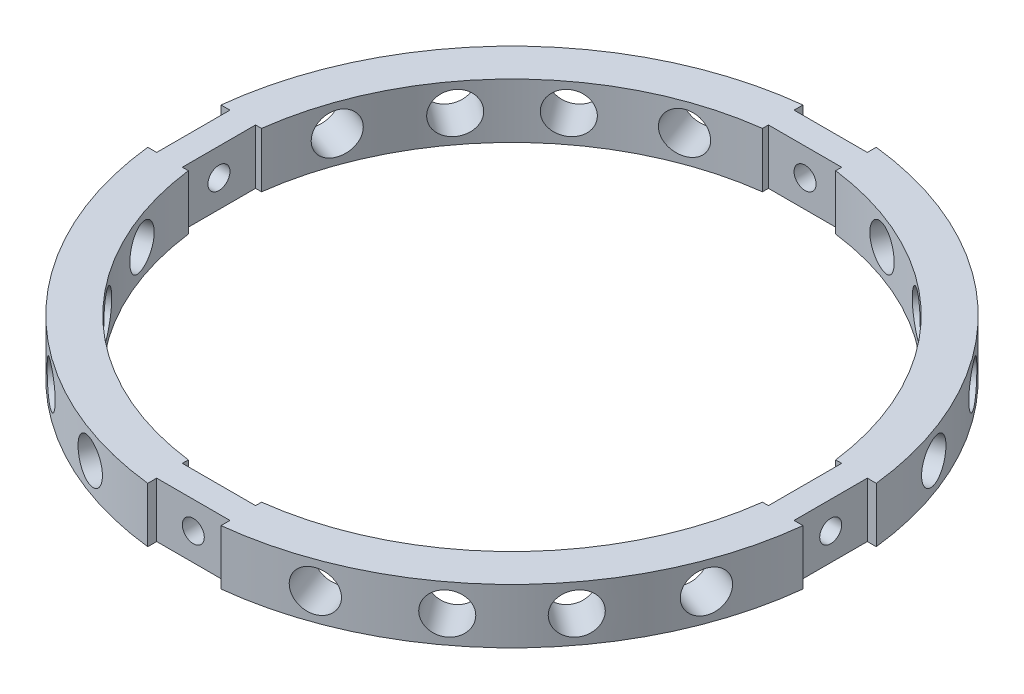
SolidWorks part; units mm, degrees
other "Markup1"
sketch "Sketch19"
material "1060 Alloy"
ref_plane "Front Plane" through (0, 0, 0) normal (0, 0, 1) x (1, 0, 0)
ref_plane "Top Plane" through (0, 0, 0) normal (0, 1, 0) x (1, 0, 0)
ref_plane "Right Plane" through (0, 0, 0) normal (1, 0, 0) x (0, 0, -1)
sketch "Sketch1" plane through (0, 0, 0) normal (0, 1, 0) x (1, 0, 0)
  circle A0 centre (0, 0) radius 90
  circle A1 centre (0, 0) radius 79
  dimension "OuterDiameter" = 180
  dimension "InnerDiameter" = 158
extrude "Boss-Extrude1" add sketch "Sketch1" along normal blind 7.5 and the other way blind 7.5
sketch "Sketch5" plane through (0, 7.5, 0) normal (0, 1, 0) x (1, 0, 0)
  line L0 (0, 0) -> (53.7588, 53.7588) construction
  line L1 (0.2616, 0.2616) -> (60.0121, 60.0121) construction
  line L2 (-121.3123, 0) -> (150.1577, 0) construction
  circle A0 centre (60.0121, 60.0121) radius 3
  circle A1 centre (60.0121, -59.4889) radius 3
  circle A2 centre (-59.4889, -59.4889) radius 3
  circle A3 centre (-59.4889, 60.0121) radius 3
  dimension "MountingBoltDiameter" = 6
  dimension "D2" = 84.5
  dimension "D3" = 45
sketch "Sketch6" plane through (0, 7.5, 0) normal (0, 1, 0) x (1, 0, 0)
  line L0 (0, -83.4209) -> (0, 77.0416) construction
  line L1 (-88.8703, 0) -> (103.6253, 0) construction
  line L2 (-10, -87) -> (10, -87)
  line L3 (-10, 90) -> (10, 90)
  line L4 (-10, 90) -> (-10, 87)
  line L5 (-10, 87) -> (10, 87)
  line L6 (10, 90) -> (10, 87)
  line L7 (-10, 90) -> (10, 87) construction
  line L8 (-10, 87) -> (10, 90) construction
  line L9 (10, -90) -> (10, -87)
  line L10 (-10, -90) -> (10, -90)
  line L11 (-10, -90) -> (-10, -87)
  line L12 (0, 0) -> (60.635, 60.635) construction
  line L13 (87, -10) -> (87, 10)
  line L14 (90, 10) -> (87, 10)
  line L15 (90, -10) -> (90, 10)
  line L16 (90, -10) -> (87, -10)
  line L17 (-90, -10) -> (-87, -10)
  line L18 (-90, -10) -> (-90, 10)
  line L19 (-90, 10) -> (-87, 10)
  line L20 (-87, -10) -> (-87, 10)
  point P5 (0, 88.5)
  point P10 (0, 90)
  dimension "RailWidth" = 20
  dimension "D1" = 90
  dimension "D2" = 3
extrude "Cut-Extrude4" cut sketch "Sketch6" against normal through all
sketch "Sketch7" plane through (-87, 0, 0) normal (-1, 0, 0) x (0, 0, 1)
  line L0 (0, 14.1508) -> (0, -8.7308) construction
  line L1 (-87, 0) -> (87, 0) construction
  line L2 (-87, -7.5) -> (-87, 7.5) construction
  line L3 (87, -7.5) -> (87, 7.5) construction
  circle A1 centre (0, 0) radius 3
  point P9 (0, 0)
  dimension "D1" = 6
extrude "Cut-Extrude5" cut sketch "Sketch7" against normal through all
sketch "Sketch12" plane through (0, 0, 87) normal (0, 0, 1) x (1, 0, 0)
  line L0 (0, 13.7216) -> (0, -16.0459) construction
  line L1 (-75.3828, 0) -> (78.5537, 0) construction
  circle A1 centre (0, 0) radius 3
  point P5 (0, 0)
  dimension "D1" = 6
extrude "Cut-Extrude8" cut sketch "Sketch12" against normal through all
sketch "Sketch13" plane through (0, 7.5, 0) normal (0, 1, 0) x (1, 0, 0)
  line L0 (0, -87.0356) -> (0, 86.4553) construction
  line L1 (-98.9563, 0) -> (122.4152, 0) construction
  line L2 (0, 0) -> (96.5387, 96.5387) construction
  line L3 (-10, -80) -> (10, -80)
  line L4 (-10, -80) -> (-10, -77)
  line L5 (-10, -77) -> (10, -77)
  line L6 (10, -80) -> (10, -77)
  line L7 (-10, -80) -> (10, -77) construction
  line L8 (-10, -77) -> (10, -80) construction
  line L9 (-10, 77) -> (10, 77)
  line L10 (10, 80) -> (10, 77)
  line L11 (-10, 80) -> (10, 80)
  line L12 (-10, 80) -> (-10, 77)
  line L13 (-77, -10) -> (-77, 10)
  line L14 (-80, 10) -> (-77, 10)
  line L15 (-80, -10) -> (-80, 10)
  line L16 (-80, -10) -> (-77, -10)
  line L17 (80, -10) -> (77, -10)
  line L18 (80, -10) -> (80, 10)
  line L19 (80, 10) -> (77, 10)
  line L20 (77, -10) -> (77, 10)
  point P7 (0, -78.5)
  dimension "D1" = 20
  dimension "D3" = 77
  dimension "D2" = 80
  dimension "D4" = 45
extrude "Cut-Extrude9" cut sketch "Sketch13" against normal through all
sketch "Sketch14" plane through (0, 7.5, 0) normal (0, 1, 0) x (1, 0, 0)
  line L0 (0, 98.1591) -> (0, -98.1685) construction
  line L1 (-142.6508, 0) -> (156.3484, 0) construction
  line L2 (0, -0.0047) -> (84.5738, 30.7777) construction
  line L3 (0, -0.0047) -> (30.7833, 84.5718) construction
  line L4 (-0.0047, 0) -> (84.5718, -30.7833) construction
  line L5 (-0.0047, 0) -> (30.7777, -84.5738) construction
  line L6 (0, 0.0047) -> (-30.7833, -84.5718) construction
  line L7 (0, 0.0047) -> (-84.5738, -30.7777) construction
  line L8 (0.0047, 0) -> (-84.5718, 30.7833) construction
  line L9 (0.0047, 0) -> (-30.7777, 84.5738) construction
  line L12 (0, -0.0047) -> (54.1656, 71.8755) construction
  line L13 (0, -0.0047) -> (71.8794, 54.1604) construction
  line L14 (-0.0047, 0) -> (54.1604, -71.8794) construction
  line L15 (-0.0047, 0) -> (71.8755, -54.1656) construction
  line L16 (0, 0.0047) -> (-71.8794, -54.1604) construction
  line L17 (0, 0.0047) -> (-54.1656, -71.8755) construction
  line L18 (0.0047, 0) -> (-54.1604, 71.8794) construction
  line L19 (0.0047, 0) -> (-71.8755, 54.1656) construction
  arc A0 (89.4427, 10) -> (10, 89.4427) centre (0, 0) ccw construction
  point P23 (0, 0)
  point P35 (0, 0)
  dimension "D1" = 20
  dimension "D2" = 20
  dimension "D4" = 17
  dimension "D5" = 17
  dimension "D3" = 4
  dimension "D6" = 4
ref_plane "Plane1" through (0.0041, 0, -0.0015) normal (0.9397, 0, -0.342) x (-0.342, 0, -0.9397)
ref_plane "Plane2" through (0.0005, 0, -0.0015) normal (0.342, 0, -0.9397) x (-0.9397, 0, -0.342)
ref_plane "Plane3" through (-0.0015, 0, -0.0041) normal (-0.342, 0, -0.9397) x (-0.9397, 0, 0.342)
ref_plane "Plane4" through (-0.0015, 0, -0.0005) normal (-0.9397, 0, -0.342) x (-0.342, 0, 0.9397)
sketch "Sketch15" plane through (0.0041, 0, -0.0015) normal (0.9397, 0, -0.342) x (-0.342, 0, -0.9397)
  line L0 (-103.0218, 0) -> (121.7701, 0) construction
  circle A0 centre (0, 0) radius 5.565
  dimension "D1" = 11.13
extrude "Cut-Extrude10" cut sketch "Sketch15" against normal through all and the other way through all
sketch "Sketch16" plane through (0.0005, 0, -0.0015) normal (0.342, 0, -0.9397) x (-0.9397, 0, -0.342)
  line L0 (-116.6479, 0) -> (178.0546, 0) construction
  circle A0 centre (0, 0) radius 5.565
  dimension "D1" = 11.13
extrude "Cut-Extrude11" cut sketch "Sketch16" against normal through all and the other way through all
sketch "Sketch17" plane through (-0.0015, 0, -0.0041) normal (-0.342, 0, -0.9397) x (-0.9397, 0, 0.342)
  line L0 (-115.4594, 0) -> (154.8622, 0) construction
  circle A0 centre (0, 0) radius 5.565
  dimension "D1" = 11.13
extrude "Cut-Extrude12" cut sketch "Sketch17" against normal through all and the other way through all
sketch "Sketch18" plane through (-0.0015, 0, -0.0005) normal (-0.9397, 0, -0.342) x (-0.342, 0, 0.9397)
  line L0 (-110.4319, 0) -> (111.3832, 0) construction
  circle A0 centre (0.4757, 0) radius 5.565
  dimension "D1" = 11.13
extrude "Cut-Extrude13" cut sketch "Sketch18" against normal through all and the other way through all
ref_plane "Plane5" through (0.003, 0, -0.0023) normal (0.7986, 0, -0.6018) x (-0.6018, 0, -0.7986)
sketch "Sketch20" plane through (0.003, 0, -0.0023) normal (0.7986, 0, -0.6018) x (-0.6018, 0, -0.7986)
  line L0 (-125.5135, 0) -> (138.902, 0) construction
  circle A0 centre (0, 0) radius 5.565
  dimension "D1" = 11.13
extrude "Cut-Extrude14" cut sketch "Sketch20" against normal through all and the other way through all
ref_plane "Plane6" through (0.0017, 0, -0.0023) normal (0.6018, 0, -0.7986) x (-0.7986, 0, -0.6018)
sketch "Sketch21" plane through (0.0017, 0, -0.0023) normal (0.6018, 0, -0.7986) x (-0.7986, 0, -0.6018)
  line L0 (-98.8665, 0) -> (107.0384, 0) construction
  circle A0 centre (0, 0) radius 5.565
  dimension "D1" = 11.13
extrude "Cut-Extrude15" cut sketch "Sketch21" against normal through all and the other way through all
ref_plane "Plane7" through (0.0023, 0, 0.0017) normal (0.7986, 0, 0.6018) x (0.6018, 0, -0.7986)
ref_plane "Plane8" through (0.0023, 0, 0.003) normal (0.6018, 0, 0.7986) x (0.7986, 0, -0.6018)
sketch "Sketch22" plane through (0.0023, 0, 0.0017) normal (0.7986, 0, 0.6018) x (0.6018, 0, -0.7986)
  line L0 (-93.4645, 0) -> (99.5843, 0) construction
  circle A0 centre (0, 0) radius 5.565
  dimension "D1" = 11.13
extrude "Cut-Extrude16" cut sketch "Sketch22" against normal through all and the other way through all
sketch "Sketch23" plane through (0.0023, 0, 0.003) normal (0.6018, 0, 0.7986) x (0.7986, 0, -0.6018)
  line L0 (-99.4077, 0) -> (99.855, 0) construction
  circle A0 centre (0, 0) radius 5.565
  dimension "D1" = 11.13
extrude "Cut-Extrude17" cut sketch "Sketch23" against normal through all and the other way through all
equation "\"InternalDiameter\"= 158mm"
equation "\"ExternalDiameter\"= 180mm"
equation "\"InnerDiameter@Sketch1\"= \"InternalDiameter\""
equation "\"OuterDiameter@Sketch1\"= \"ExternalDiameter\""
equation "\"MountingBoltDiameter\"= 6mm"
equation "\"NumberOfMountingBolts\"= 4"
equation "\"MountingBoltDiameter@Sketch5\"= \"MountingBoltDiameter\""
equation "\"D1@Sketch5\"= \"NumberOfMountingBolts\""
equation "\"D2@Sketch5\"= 0.25 * ( \"InternalDiameter\" + \"ExternalDiameter\" )"
equation "\"RailBoltDiameter\"= 6mm"
equation "\"RailBoltSpacing\"= 12mm"
equation "\"RailWidth\"= 10mm"
equation "\"RailWidth@Sketch6\"= \"RailWidth\" * 2"
equation "\"D1@Sketch13\"= \"RailWidth\" * 2"
equation "\"RailDepth\"= 2mm"
equation "\"D3@Sketch13\"= \"InternalDiameter\" / 2 - \"RailDepth\""
equation "\"D2@Sketch13\"= \"InternalDiameter\" / 2 + \"RailDepth\" / 2"
equation "\"D1@Sketch6\"= \"ExternalDiameter\" / 2"
equation "\"D2@Sketch6\"= \"RailDepth\" * 1.5"
equation "\"TurnlockDiameter\"= 11.13mm"
equation "\"D1@Sketch15\"= \"TurnlockDiameter\""
equation "\"D1@Sketch16\"= \"D1@Sketch15\""
equation "\"D1@Sketch17\"= \"D1@Sketch16\""
equation "\"D1@Sketch18\"= \"D1@Sketch17\""
equation "\"D1@Sketch7\"= \"RailBoltDiameter\""
equation "\"D1@Sketch12\"= \"D1@Sketch7\""
equation "\"D1@Sketch20\"= \"D1@Sketch18\""
equation "\"D1@Sketch21\"= \"D1@Sketch20\""
equation "\"D1@Sketch22\"= \"D1@Sketch21\""
equation "\"D1@Sketch23\"= \"D1@Sketch22\""
